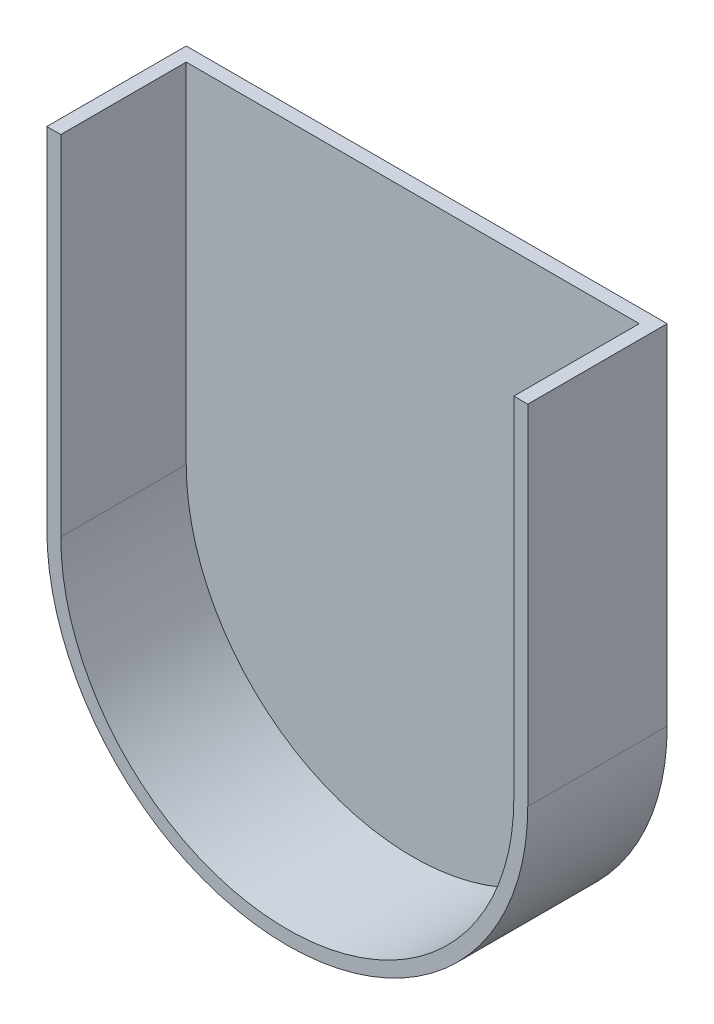
SolidWorks part; units mm, degrees
material "Thornel Mat VMA"
ref_plane "Płaszczyzna przednia" through (0, 0, 0) normal (0, 0, 1) x (1, 0, 0)
ref_plane "Płaszczyzna górna" through (0, 0, 0) normal (0, 1, 0) x (1, 0, 0)
ref_plane "Płaszczyzna prawa" through (0, 0, 0) normal (1, 0, 0) x (0, 0, -1)
sketch "Szkic1" plane through (0, 0, 0) normal (0, 0, 1) x (1, 0, 0)
  line L0 (34.5, 0) -> (34.5, 50)
  line L2 (32.5, 0) -> (32.5, 50)
  line L3 (32.5, 50) -> (-32.5, 50)
  line L4 (-32.5, 0) -> (-32.5, 50)
  line L5 (-34.5, 0) -> (-34.5, 50)
  line L6 (-34.5, 50) -> (34.5, 50)
  arc A0 (-32.5, 0) -> (32.5, 0) centre (0, 0) ccw
  arc A1 (-34.5, 0) -> (34.5, 0) centre (0, 0) ccw
  dimension "D1" = 65
  dimension "D2" = 50
  dimension "D3" = 2
extrude "Dodanie-wyciągnięcie1" add sketch "Szkic1" along normal blind 20 contours L5 A1 L0 L6 L2 A0 L4 region at (0, -33.4091, 0)
extrude "Dodanie-wyciągnięcie2" add sketch "Szkic1<3>" along normal blind 2 contours L4 A0 L2 L3 region at (0, 11.8889, 0)
sketch "Szkic1<3>" plane through (0, 0, 0) normal (0, 0, 1) x (1, 0, 0) same geometry as "Szkic1"
